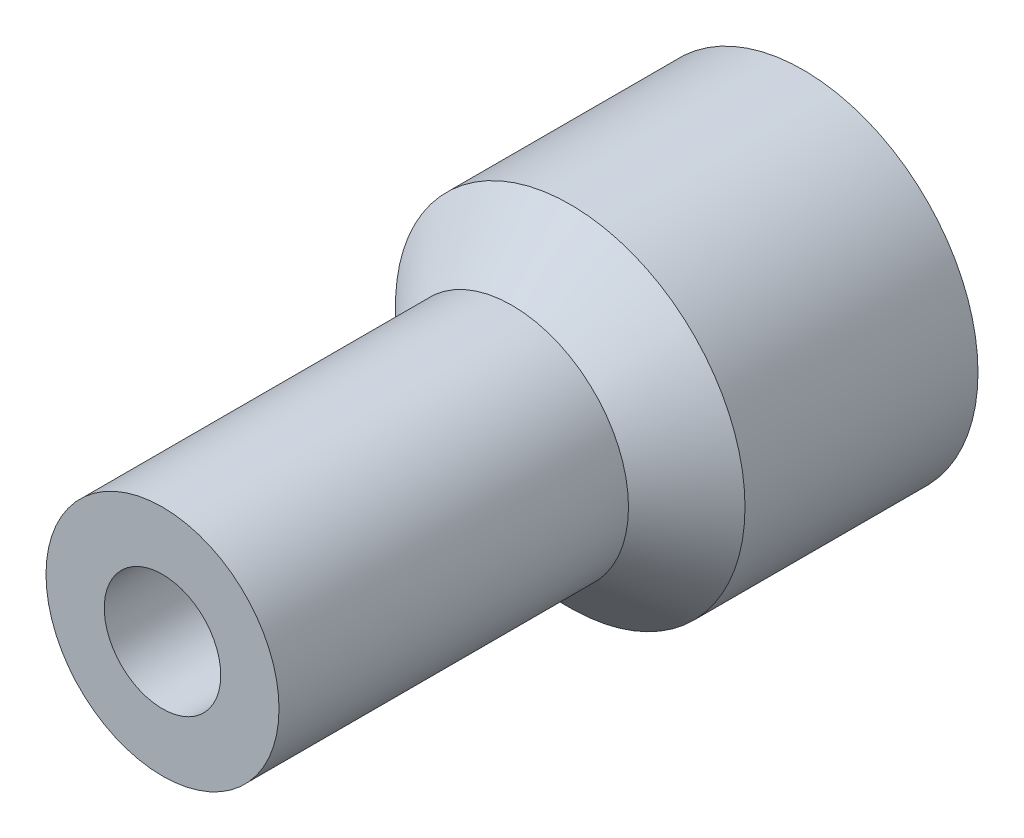
SolidWorks part; units mm, degrees
material "Custom Plastic"
ref_plane "X-Y Datum" through (0, 0, 0) normal (0, 0, 1) x (1, 0, 0)
ref_plane "X-Z Datum" through (0, 0, 0) normal (0, 1, 0) x (1, 0, 0)
ref_plane "Y-Z Datum" through (0, 0, 0) normal (1, 0, 0) x (0, 0, -1)
sketch "Base Sketch" plane through (0, 0, 0) normal (0, 0, 1) x (1, 0, 0)
  circle A0 centre (0, 0) radius 3
  circle A1 centre (0, 0) radius 2
  circle A2 centre (0, 0) radius 1
  dimension "D1" = 6
  dimension "D2" = 4
  dimension "D3" = 2
extrude "Extrude Pin Thick" add sketch "Base Sketch" along normal blind 4 contours A0 A1 region at (-2.9151, 0, 0)
extrude "Extrude Pin Thin" add sketch "Base Sketch<3>" along normal blind 11 contours A1 A2 region at (-1.9434, 0, 0)
sketch "Base Sketch<3>" plane through (0, 0, 0) normal (0, 0, 1) x (1, 0, 0) same geometry as "Base Sketch"
chamfer "Chamfer" distance 1 angle 45 1 edges at (2, 0, 4)
